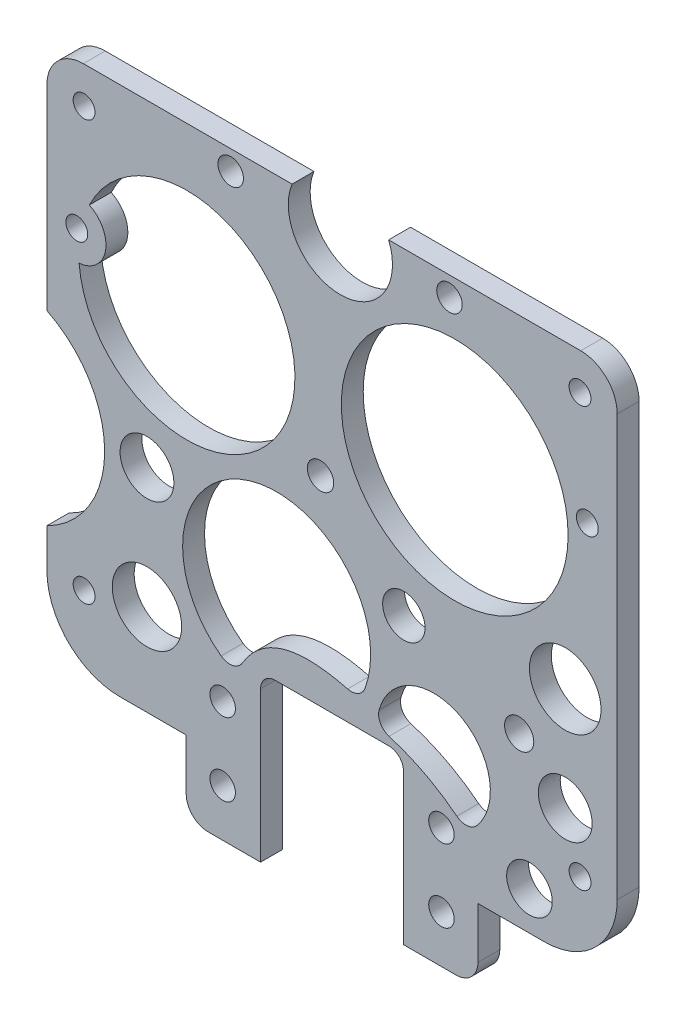
SolidWorks part; units mm, degrees
ref_plane "前视基准面" through (0, 0, 0) normal (0, 0, 1) x (1, 0, 0)
ref_plane "上视基准面" through (0, 0, 0) normal (0, 1, 0) x (1, 0, 0)
ref_plane "右视基准面" through (0, 0, 0) normal (1, 0, 0) x (0, 0, -1)
sketch "草图1" plane through (0, 0, 0) normal (0, 0, 1) x (1, 0, 0)
  line L1 (-88, -40) -> (88, -40)
  line L2 (-88, -40) -> (-88, 40)
  line L3 (-88, 40) -> (88, 40)
  line L4 (88, -40) -> (88, 40)
  line L5 (-88, -40) -> (88, 40) construction
  line L6 (-88, 40) -> (88, -40) construction
  point P0 (0, 0)
  dimension "D1" = 80
  dimension "D2" = 176
extrude "凸台-拉伸1" add sketch "草图1" along normal blind 3
sketch "草图2" plane through (0, 0, 0) normal (0, 0, -1) x (-1, 0, 0)
  line L4 (77.0286, 36.7917) -> (56.9392, 54.3699)
  line L5 (56.9392, 54.3699) -> (101.0286, 54.3699)
  line L6 (101.0286, 54.3699) -> (101.0286, 15.7917)
  line L7 (0, 40) -> (0, -40) construction
  line L9 (77.0286, 36.7917) -> (101.0286, 15.7917)
  line L10 (-23, 40.7423) -> (-23, 20.7423)
  line L11 (23, 20) -> (23, 40)
  line L12 (-88, 40) -> (88, 40) construction
  line L13 (88, -40) -> (-88, -40) construction
  line L17 (-23, 20.7423) -> (-23, 17.7423)
  line L19 (23, 17.7423) -> (23, 20)
  line L20 (-23, 40.7423) -> (23, 40)
  line L21 (23, 40) -> (23, 15) construction
  line L22 (23, 17.7423) -> (23, 15)
  line L23 (23, 15) -> (-23, 15)
  line L24 (-23, 15) -> (-23, 17.7423)
  circle A4 centre (65, 30) radius 1.75
  circle A5 centre (35, 30) radius 1.75
  circle A6 centre (-35, 30) radius 1.75
  circle A7 centre (-65, 30) radius 1.75
  dimension "D1" = 3
  dimension "D2" = 25
extrude "切除-拉伸1" cut sketch "草图2" against normal blind 3
sketch "草图3" plane through (0, 0, 0) normal (0, 0, -1) x (-1, 0, 0)
  line L8 (0, 15) -> (0, -40) construction
  line L9 (-23, 15) -> (23, 15) construction
  line L10 (88, -40) -> (-88, -40) construction
  circle A12 centre (-74.5578, -16.995) radius 2
extrude "切除-拉伸2" cut sketch "草图3" against normal blind 3
fillet "圆角2" radius 20 1 edges at (-88, -40, 1.5)
fillet "圆角3" radius 10 1 edges at (88, -40, 1.5)
sketch "草图7" plane through (0, 0, 3) normal (0, 0, 1) x (1, 0, 0)
  line L1 (-23, 40) -> (23, 40)
  line L2 (-23, 40) -> (-23, 15)
  line L3 (-23, 15) -> (23, 15)
  line L4 (23, 40) -> (23, 15)
extrude "凸台-拉伸2" add sketch "草图7" against normal up to surface (3 mm away) up to face at (76.5578, -16.995, 0)
sketch "草图8" plane through (0, 0, 3) normal (0, 0, 1) x (1, 0, 0)
  circle A4 centre (-15.6, -14.7419) radius 1.75
  circle A5 centre (-15.6, -0.7419) radius 1.75
  circle A6 centre (-76.6, -14.7419) radius 1.75
  circle A7 centre (-76.6, -0.7419) radius 1.75
extrude "切除-拉伸5" cut sketch "草图8" against normal blind 10
sketch "草图9" plane through (0, 0, 3) normal (0, 0, 1) x (1, 0, 0)
  circle A4 centre (14.9, 27.6805) radius 1.5
  circle A5 centre (14.9, -29.8195) radius 1.5
  circle A7 centre (82.9, 27.6805) radius 1.5
extrude "切除-拉伸6" cut sketch "草图9" against normal blind 10
sketch "草图10" plane through (0, 0, 3) normal (0, 0, 1) x (1, 0, 0)
  line L0 (-76.6, -0.7419) -> (-15.6, -0.7419) construction
  line L1 (-46.1, -0.7419) -> (-46.1, -7.7419) construction
  line L2 (-15.6, -0.7419) -> (88, -0.7419) construction
  line L8 (-71.1, -28.7419) -> (-21.1, -28.7419)
  line L9 (88, -30) -> (88, 40) construction
  line L10 (-71.1, -28.7419) -> (-71.1, 13.2581)
  line L12 (-71.1, 13.2581) -> (-21.1, 13.2581)
  line L13 (-21.1, -28.7419) -> (-21.1, 13.2581)
  line L14 (-71.1, -28.7419) -> (-21.1, 13.2581) construction
  line L15 (-71.1, 13.2581) -> (-21.1, -28.7419) construction
  circle A0 centre (28.9878, 9.8968) radius 14.8228
  circle A1 centre (65.7188, 9.8968) radius 15.5479
  circle A2 centre (41.2999, -17.8053) radius 12.8901
  circle A3 centre (62.846, -25.8081) radius 7.757
  circle A6 centre (-21.0474, 29.9939) radius 6.9346
  circle A7 centre (1.1607, 29.9939) radius 7.0296
  circle A8 centre (50.0387, 29.9939) radius 7.1439
  circle A9 centre (-49.9, 31.0348) radius 6.5819
  circle A10 centre (3.4638, -11.9262) radius 14.2554
  circle A11 centre (-5.846, 14.7618) radius 5.8843
  dimension "D1" = 7
  dimension "D2" = 42
  dimension "D3" = 50
sketch "草图12" plane through (0, 0, 0) normal (0, 0, -1) x (-1, 0, 0)
  circle A4 centre (6.363, -26) radius 1.5
  circle A5 centre (6.363, -36) radius 1.5
  circle A6 centre (36.363, -26) radius 1.5
  circle A7 centre (36.363, -36) radius 1.5
extrude "切除-拉伸9" cut sketch "草图12" against normal blind 4
extrude "切除-拉伸10" cut sketch "草图10" against normal blind 10
fillet "圆角4" radius 10 4 edges at (-71.1, 13.2581, 1.5) (-71.1, -28.7419, 1.5) (-21.1, -28.7419, 1.5) (-21.1, 13.2581, 1.5)
sketch "草图13" plane through (0, 0, 0) normal (0, 0, -1) x (-1, 0, 0)
  line L0 (-82.9, 27.6805) -> (-14.9, 27.6805) construction
  line L1 (-48.9, 27.6805) -> (-48.9, 49.6049) construction
  line L2 (-88, -30) -> (-88, 40) construction
  line L6 (-9.8, -30) -> (-9.8, 40)
  line L8 (-88, 40) -> (73.3619, 40) construction
  line L10 (-9.8, 40) -> (97.7933, 40)
  line L11 (-9.8, 40) -> (-9.8, -56.684)
  line L12 (-9.8, -56.684) -> (97.7933, -56.684)
  line L13 (97.7933, 40) -> (97.7933, -56.684)
extrude "切除-拉伸11" cut sketch "草图13" against normal blind 10
fillet "圆角5" radius 10 3 edges at (9.8, -40, 1.5)
sketch "草图15" plane through (0, 0, 0) normal (0, 0, -1) x (-1, 0, 0)
  line L0 (-9.8, -30) -> (-88, -30) construction
  line L1 (-48.9, -30) -> (-28.9, -30) construction
  line L2 (-48.9, -30) -> (-48.9, -35) construction
  line L3 (-48.9, -35) -> (-28.9, -35) construction
  line L5 (-28.9, -35) -> (-68.9, -35)
  line L6 (-28.9, -35) -> (-28.9, -50)
  line L7 (-28.9, -50) -> (-68.9, -50)
  line L8 (-68.9, -35) -> (-68.9, -50)
  dimension "D1" = 20
  dimension "D2" = 5
  dimension "D3" = 15
  dimension "D4" = 40
extrude "凸台-拉伸4" add sketch "草图15" against normal blind 3
fillet "圆角8" radius 3 2 edges at (28.9, -50, 1.5) (68.9, -50, 1.5)
sketch "草图16" plane through (0, 0, 0) normal (0, 0, -1) x (-1, 0, 0)
  circle A4 centre (-63.9, -33.5) radius 1.75
  circle A5 centre (-33.9, -43.5) radius 1.75
  circle A6 centre (-63.9, -43.5) radius 1.75
  circle A7 centre (-33.9, -33.5) radius 1.75
extrude "切除-拉伸12" cut sketch "草图16" against normal blind 10
sketch "草图17" plane through (0, 0, 0) normal (0, 0, -1) x (-1, 0, 0)
  line L13 (-39.1, -40.75) -> (-39.1, -55.483)
  line L14 (-39.1, -55.483) -> (-58.7, -55.483)
  line L15 (-58.7, -40.75) -> (-58.7, -55.483)
  line L16 (-58.7, -40.75) -> (-58.7, -27.4)
  line L17 (-54.7, -27.4) -> (-58.7, -27.4)
  line L18 (-43.1, -27.4) -> (-54.7, -27.4)
  line L19 (-43.1, -27.4) -> (-39.1, -27.4)
  line L20 (-39.1, -40.75) -> (-39.1, -27.4)
extrude "切除-拉伸13" cut sketch "草图17" against normal blind 10
sketch "草图18" plane through (0, 0, 0) normal (0, 0, -1) x (-1, 0, 0)
  line L0 (-49.9079, -27.4) -> (-38.52, -27.4) construction
  line L1 (-39.1, -30.5063) -> (-39.1, -27.4) construction
  line L2 (-55.254, -27.4) -> (-58.7, -27.4)
  line L3 (-39.1, -27.4) -> (-49.9079, -27.4)
  line L4 (-39.1, -27.4) -> (-39.1, -30.5063)
  line L6 (-58.7, -27.4) -> (-58.7, -32.3642)
  arc A0 (-39.1, -30.5063) -> (-49.9079, -27.4) centre (-41.2999, -17.8053) ccw construction
  arc A1 (-55.254, -27.4) -> (-65.5943, -33.062) centre (-62.846, -25.8081) ccw construction
  arc A2 (-62.1503, -33.5339) -> (-65.5943, -33.062) centre (-63.9, -33.5) ccw
  arc A3 (-67.2982, -32.1602) -> (-65.5943, -33.062) centre (-62.846, -25.8081) ccw
  arc A4 (-52.6449, -23.9246) -> (-49.9079, -27.4) centre (-41.2999, -17.8053) ccw
  arc A5 (-39.1, -30.5063) -> (-35.7066, -29.4187) centre (-41.2999, -17.8053) ccw
  arc A6 (-55.254, -27.4) -> (-55.0889, -25.8081) centre (-62.846, -25.8081) ccw
  arc A7 (-62.1503, -33.5339) -> (-58.7, -32.3642) centre (-62.846, -25.8081) ccw
  spline S0 degree 2 poles (-52.6449, -23.9246) (-39.6139, -19.8261) (-35.7066, -29.4187) knots 0 0 0 1 1 1
  spline S1 degree 2 poles (-67.2982, -32.1602) (-61.9758, -27.4488) (-55.0889, -25.8081) knots 0 0 0 1 1 1
extrude "凸台-拉伸5" add sketch "草图18" against normal blind 3
fillet "圆角9" radius 2 2 edges at (39.1, -27.4, 1.5) (58.7, -27.4, 1.5)
fillet "圆角10" radius 2 4 edges at (35.7066, -29.4187, 1.5) (52.6449, -23.9246, 1.5) (55.0889, -25.8081, 1.5) (67.2982, -32.1602, 1.5)
sketch "草图20" plane through (0, 40, 0) normal (0, 1, 0) x (1, 0, 0)
  line L4 (9.8, 0) -> (9.8, -3)
  line L5 (9.8, -3) -> (88, -3)
  line L6 (88, -3) -> (88, 0)
  line L7 (88, 0) -> (9.8, 0)
  line L8 (9.8, 0) -> (9.8, -3)
  line L9 (9.8, -3) -> (88, -3)
  line L10 (88, -3) -> (88, 0)
  line L11 (88, 0) -> (9.8, 0)
  dimension "D1" = 0
extrude "凸台-拉伸6" add sketch "草图20" along normal blind 10
sketch "草图21" plane through (0, 0, 0) normal (0, 0, -1) x (-1, 0, 0)
  line L0 (-88, 50) -> (-88, 40) construction
  line L1 (-88, -30) -> (-88, 50) construction
  line L2 (-88, 40) -> (-9.8, 40) construction
  line L3 (-9.8, 0.8436) -> (-9.8, 50) construction
  line L4 (-48.9, 40) -> (-13.9, 40) construction
  line L5 (-48.9, 40) -> (-48.9, 50) construction
  line L6 (-88, 50) -> (-9.8, 50) construction
  circle A0 centre (-13.9, 40) radius 1.5
  circle A1 centre (-83.9, 40) radius 1.5
  dimension "D3" = 3
  dimension "D1" = 10
  dimension "D2" = 35
extrude "切除-拉伸14" cut sketch "草图21" against normal blind 8
chamfer "倒角1" distance 8 angle 60 2 edges at (9.8, 50, 1.5) (88, 50, 1.5)
sketch "草图23" plane through (0, 0, 0) normal (0, 0, -1) x (-1, 0, 0)
  line L0 (-48.9, 50) -> (-48.9, -59.6497) construction
  line L1 (-74.1436, 50) -> (-23.6564, 50) construction
  circle A0 centre (-14.9, -29.8195) radius 1.5 construction
  circle A1 centre (-14.9, -29.8195) radius 1.5
  circle A2 centre (-82.9, -29.8195) radius 1.5
extrude "切除-拉伸15" cut sketch "草图23" against normal blind 8
sketch "草图24" plane through (0, 0, 0) normal (0, 0, -1) x (-1, 0, 0)
  circle A0 centre (-80.8724, -8.5387) radius 4.9059
  circle A1 centre (-58.7411, -10.9184) radius 2.9048
  circle A2 centre (-23.5214, -10.9184) radius 3.6886
  circle A3 centre (-23.5214, -27.4574) radius 4.7594
  circle A4 centre (-75.9665, -34.7155) radius 3.1301
  circle A5 centre (-80.8724, -22.698) radius 3.6886
  circle A6 centre (-47.3185, 0) radius 1.8131
extrude "切除-拉伸16" cut sketch "草图24" against normal blind 8
sketch "草图25" plane through (0, 0, 0) normal (0, 0, -1) x (-1, 0, 0)
  line L0 (-82.9, 27.6805) -> (-82.9, 32.6805) construction
  line L1 (-82.9, 32.6805) -> (-88, 32.6805) construction
  line L2 (-88, -30) -> (-88, 42) construction
  line L4 (-88, 32.6805) -> (-4.0955, 32.6805)
  line L5 (-88, 32.6805) -> (-88, 57.069)
  line L6 (-88, 57.069) -> (-4.0955, 57.069)
  line L7 (-4.0955, 32.6805) -> (-4.0955, 57.069)
  dimension "D1" = 5
extrude "切除-拉伸17" cut sketch "草图25" against normal blind 10
fillet "圆角11" radius 5 2 edges at (9.8, 32.6805, 1.5) (88, 32.6805, 1.5)
sketch "草图26" plane through (0, 0, 0) normal (0, 0, -1) x (-1, 0, 0)
  line L0 (-83, 32.6805) -> (-88, 32.6805) construction
  line L1 (-88, 32.6805) -> (-88, 12.6805) construction
  line L2 (-88, 12.6805) -> (-9.8, 12.6805) construction
  line L3 (-9.8, 0.8436) -> (-9.8, 27.6805) construction
  line L4 (-48.9, 12.6805) -> (-83.9, 12.6805) construction
  line L5 (-48.9, 12.6805) -> (-13.9, 12.6805) construction
  circle A0 centre (-83.9, 12.6805) radius 1.5
  circle A1 centre (-13.9, 12.6805) radius 1.5
  dimension "D3" = 3
  dimension "D5" = 3
  dimension "D1" = 20
  dimension "D2" = 35
  dimension "D4" = 35
extrude "切除-拉伸18" cut sketch "草图26" against normal blind 10
sketch "草图27" plane through (0, 0, 0) normal (0, 0, -1) x (-1, 0, 0)
  arc A0 (-14.7252, 13.9332) -> (-14.2238, 11.2159) centre (-13.9, 12.6805) ccw
  arc A1 (-15.6163, 16.2936) -> (-14.214, 8.6929) centre (-13.9, 12.6805) ccw
  arc A2 (-14.214, 8.6929) -> (-14.2238, 11.2159) centre (-28.9878, 9.8968) ccw
  arc A3 (-14.7252, 13.9332) -> (-15.6163, 16.2936) centre (-28.9878, 9.8968) ccw
extrude "凸台-拉伸7" add sketch "草图27" against normal blind 3
